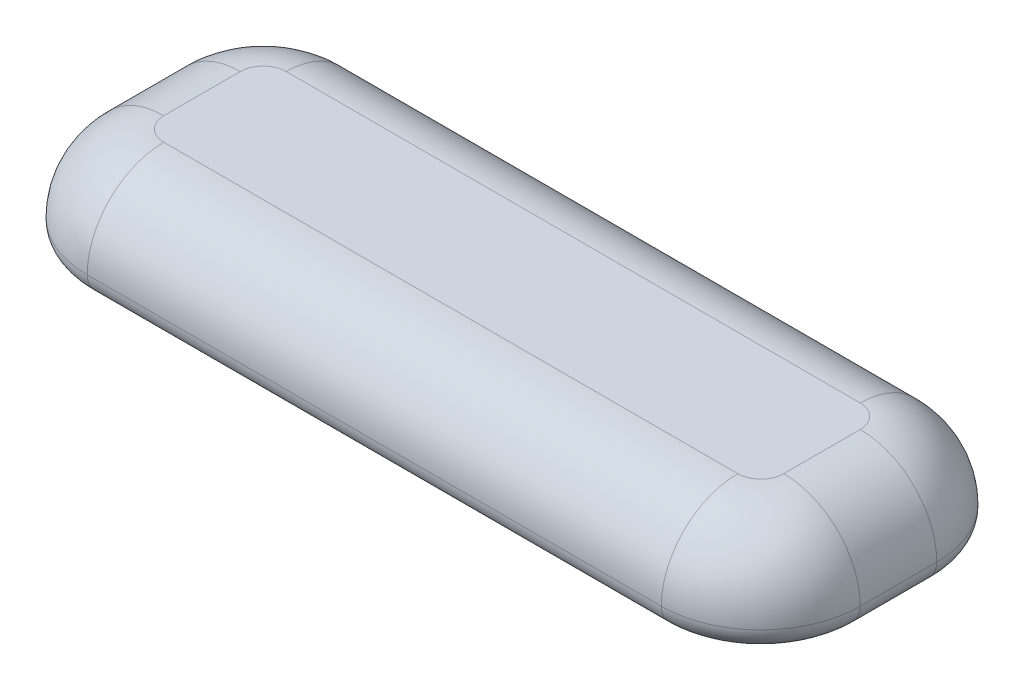
SolidWorks part; units mm, degrees
ref_plane "前视基准面" through (0, 0, 0) normal (0, 0, 1) x (1, 0, 0)
ref_plane "上视基准面" through (0, 0, 0) normal (0, 1, 0) x (1, 0, 0)
ref_plane "右视基准面" through (0, 0, 0) normal (1, 0, 0) x (0, 0, -1)
sketch "草图1" plane through (0, 0, 0) normal (0, 1, 0) x (1, 0, 0)
  line L1 (-37.5, 15) -> (37.5, 15)
  line L2 (-47.5, 5) -> (-47.5, -5)
  line L3 (-37.5, -15) -> (37.5, -15)
  line L4 (47.5, 5) -> (47.5, -5)
  line L5 (0, -15) -> (0, 15) construction
  line L6 (-47.5, 0) -> (47.5, 0) construction
  arc A0 (-47.5, -5) -> (-37.5, -15) centre (-37.5, -5) ccw
  arc A1 (-47.5, 5) -> (-37.5, 15) centre (-37.5, 5) cw
  arc A2 (37.5, 15) -> (47.5, 5) centre (37.5, 5) cw
  arc A3 (47.5, -5) -> (37.5, -15) centre (37.5, -5) cw
  point P0 (0, 0)
  point P8 (-47.5, 15)
  point P11 (47.5, 15)
  point P15 (47.5, -15)
  dimension "D3" = 10
  dimension "D1" = 95
  dimension "D2" = 30
extrude "凸台-拉伸1" add sketch "草图1" along normal blind 10
shell "抽壳2" thickness 3 removed face at (0, 0, 0) outward yes
fillet "圆角3" radius 10 8 edges at (46.6924, 13, -14.1924) (50.5, 13, 0) (46.6924, 13, 14.1924) (0, 13, 18) (-46.6924, 13, 14.1924) (-50.5, 13, 0) (-46.6924, 13, -14.1924) (0, 13, -18)
fillet "圆角4" radius 3 8 edges at (50.5, 0, 0) (46.6924, 0, 14.1924) (0, 0, 18) (-46.6924, 0, 14.1924) (-50.5, 0, 0) (-46.6924, 0, -14.1924) (0, 0, -18) (46.6924, 0, -14.1924)
ref_plane "基准面1" through (0, 10, 0) normal (0, -1, 0) x (-1, 0, 0)
sketch "草图2" plane through (0, 10, 0) normal (0, -1, 0) x (-1, 0, 0)
  line L0 (0, 0) -> (36.6, 0) construction
  line L1 (0, 0) -> (0, 6.5357) construction
  line L2 (34.55, 0.55) -> (38.65, 0.55)
  line L3 (34.55, 0.55) -> (34.55, -0.55)
  line L4 (34.55, -0.55) -> (38.65, -0.55)
  line L5 (38.65, 0.55) -> (38.65, -0.55)
  line L6 (36.6, -0.55) -> (36.6, 0.55) construction
  line L7 (34.55, 0) -> (38.65, 0) construction
  line L8 (36.05, 2.05) -> (37.15, 2.05)
  line L9 (36.05, 2.05) -> (36.05, -2.05)
  line L10 (36.05, -2.05) -> (37.15, -2.05)
  line L11 (37.15, 2.05) -> (37.15, -2.05)
  line L12 (36.6, -2.05) -> (36.6, 2.05) construction
  line L13 (36.05, 0) -> (37.15, 0) construction
  line L14 (-36.05, 0) -> (-37.15, 0) construction
  line L15 (-36.6, -2.05) -> (-36.6, 2.05) construction
  line L16 (-34.55, 0) -> (-38.65, 0) construction
  line L17 (-36.6, -0.55) -> (-36.6, 0.55) construction
  line L18 (-37.15, 2.05) -> (-37.15, -2.05)
  line L19 (-36.05, -2.05) -> (-37.15, -2.05)
  line L20 (-36.05, 2.05) -> (-36.05, -2.05)
  line L21 (-36.05, 2.05) -> (-37.15, 2.05)
  line L22 (-38.65, 0.55) -> (-38.65, -0.55)
  line L23 (-34.55, -0.55) -> (-38.65, -0.55)
  line L24 (-34.55, 0.55) -> (-34.55, -0.55)
  line L25 (-34.55, 0.55) -> (-38.65, 0.55)
  circle A0 centre (36.6, 0) radius 2.65
  circle A1 centre (-36.6, 0) radius 2.65
  dimension "D2" = 5.3
  dimension "D1" = 36.6
  dimension "D3" = 4.1
  dimension "D4" = 1.1
  dimension "D5" = 4.1
  dimension "D6" = 1.1
extrude "凸台-拉伸2" add sketch "草图2" along normal blind 8 contours A0 L8 L11 L2 L5 L4 L10 L9 L3 | A1 L25 L24 L23 L20 L19 L18 L22 L21 region at (-34.025, 10, 0) region at (39.175, 10, 0)
fillet "圆角7" radius 5 8 edges at (0, 10, 15) (44.5711, 10, 12.0711) (47.5, 10, 0) (44.5711, 10, -12.0711) (0, 10, -15) (-44.5711, 10, -12.0711) (-47.5, 10, 0) (-44.5711, 10, 12.0711)
chamfer "倒角1" distance 0.2 angle 45 12 edges at (36.6, 2, -2.05) (36.05, 2, -1.3) (35.3, 2, -0.55) (34.55, 2, 0) (35.3, 2, 0.55) (36.05, 2, 1.3) (36.6, 2, 2.05) (37.15, 2, 1.3) (37.9, 2, 0.55) (38.65, 2, 0) (37.9, 2, -0.55) (37.15, 2, -1.3)
chamfer "倒角2" distance 0.2 angle 45 12 edges at (-36.05, 2, -1.3) (-35.3, 2, -0.55) (-34.55, 2, 0) (-35.3, 2, 0.55) (-36.05, 2, 1.3) (-36.6, 2, 2.05) (-37.15, 2, 1.3) (-37.9, 2, 0.55) (-38.65, 2, 0) (-37.9, 2, -0.55) (-37.15, 2, -1.3) (-36.6, 2, -2.05)
fillet "圆角9" radius 2 1 edges at (36.6, 10, -2.65)
fillet "圆角10" radius 2 1 edges at (-36.6, 10, 2.65)
